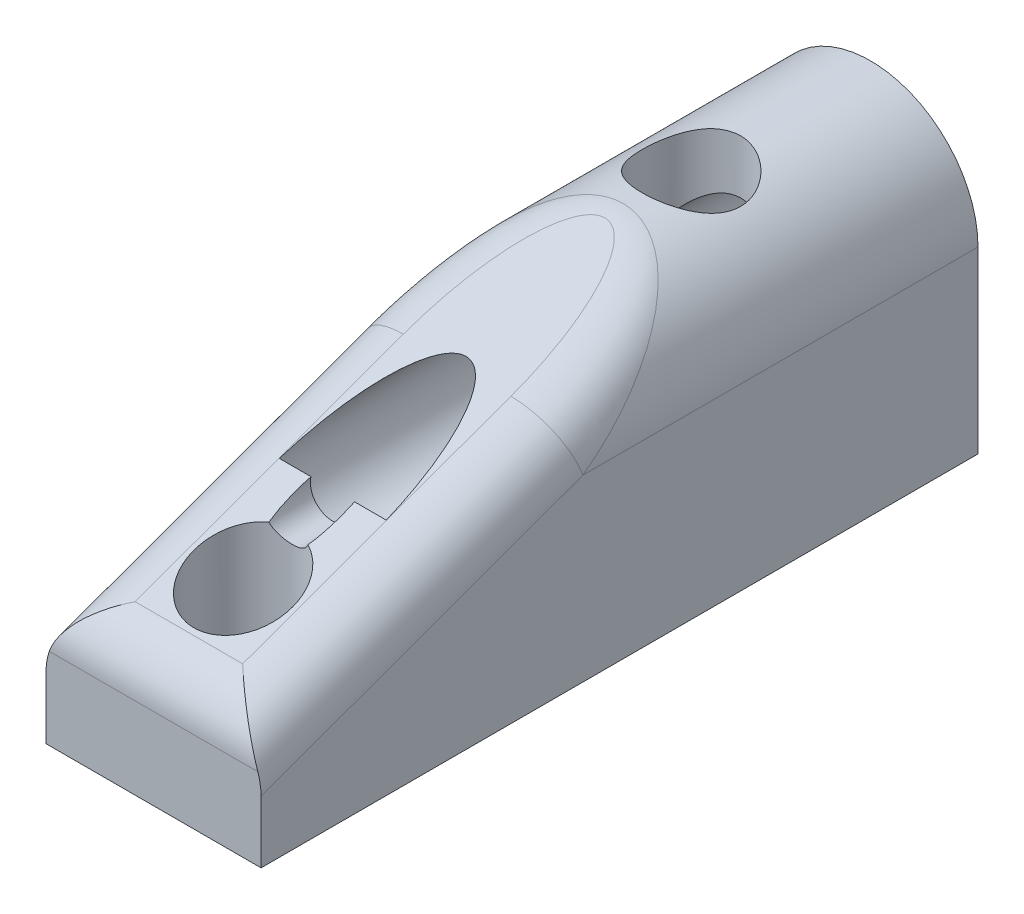
SolidWorks part; units mm, degrees
ref_plane "Ebene vorne" through (0, 0, 0) normal (0, 0, 1) x (1, 0, 0)
ref_plane "Ebene oben" through (0, 0, 0) normal (0, 1, 0) x (1, 0, 0)
ref_plane "Ebene rechts" through (0, 0, 0) normal (1, 0, 0) x (0, 0, -1)
sketch "Skizze1" plane through (0, 0, 0) normal (0, 0, 1) x (1, 0, 0)
  line L1 (-63.0762, -14.2199) -> (-23.0762, -14.2199)
  line L2 (-63.0762, -14.2199) -> (-63.0762, -26.2199)
  line L3 (-63.0762, -26.2199) -> (-23.0762, -26.2199)
  line L4 (-23.0762, -14.2199) -> (-23.0762, -26.2199)
  dimension "D1" = 12
  dimension "D2" = 40
extrude "Aufsatz-Linear austragen1" add sketch "Skizze1" along normal blind 63
sketch "Skizze2" plane through (0, 0, 0) normal (0, 0, -1) x (-1, 0, 0)
  line L0 (32.9762, -26.2199) -> (32.9762, -24.2199)
  line L1 (63.0762, -26.2199) -> (23.0762, -26.2199) construction
  line L2 (32.9762, -24.2199) -> (30.0063, -21.25)
  line L3 (30.0063, -21.25) -> (32.9762, -18.2802)
  line L4 (32.9762, -18.2802) -> (53.1762, -18.2802)
  line L5 (53.1762, -18.2802) -> (56.146, -21.25)
  line L6 (56.146, -21.25) -> (53.1762, -24.2199)
  line L7 (53.1762, -24.2199) -> (53.1762, -26.2199)
  line L9 (23.0762, -26.2199) -> (23.0762, -14.2199) construction
  dimension "D1" = 4.2
  dimension "D2" = 20.2
  dimension "D3" = 135
  dimension "D4" = 9.9
  dimension "D5" = 2
extrude "Schnitt-Linear austragen2" cut sketch "Skizze2" against normal through all and the other way through all flip side to cut
ref_plane "Ebene1" through (-43.0762, 0, 0) normal (1, 0, 0) x (0, 0, -1)
ref_axis "Achse1" through (-43.0762, -14.2199, 63) along (0, 1, 0)
hole_wizard "Stirnsenkung für M3" positions "Skizze12" profile "Skizze11" counterbore size "M4" standard "ISO" end condition through all
sketch "Skizze12" plane through (-23.0762, 0, 0) normal (1, 0, 0) x (0, 0, -1)
  line L0 (-63, -26.2199) -> (-63, -14.2199) construction
  line L1 (-63, -26.2199) -> (0, -26.2199) construction
  point P2 (-51, -21.2199)
  dimension "D1" = 12
  dimension "D2" = 5
sketch "Skizze11" plane through (-23.0762, -21.2199, 51) normal (0, 1, 0) x (0, 0, -1)
  line L0 (0, 0) -> (0, 40)
  line L1 (0, 40) -> (2.25, 40)
  line L3 (2.25, 40) -> (2.25, 4.4)
  line L4 (2.25, 4.4) -> (4, 4.4)
  line L5 (4, 4.4) -> (4, 0)
  line L7 (4, 0) -> (0, 0)
  line L11 (0, -6.35) -> (0, 107.95) construction
  dimension "Bohrerdurchmesser" = 4.5
  dimension "Bohrungstiefe" = 40
  dimension "Senkdurchmesser2" = 8
  dimension "Senktiefe2" = 4.4
sketch "Skizze13" plane through (-63.0762, 0, 0) normal (-1, 0, 0) x (0, 0, 1)
  line L1 (46.9585, -21.2199) -> (48.9793, -24.7199)
  line L2 (48.9793, -24.7199) -> (53.0207, -24.7199)
  line L3 (53.0207, -24.7199) -> (55.0415, -21.2199)
  line L4 (55.0415, -21.2199) -> (53.0207, -17.7199)
  line L5 (53.0207, -17.7199) -> (48.9793, -17.7199)
  line L6 (48.9793, -17.7199) -> (46.9585, -21.2199)
  circle A0 centre (51, -21.2199) radius 3.5 construction
  dimension "D1" = 7
extrude "Schnitt-Linear austragen3" cut sketch "Skizze13" against normal blind 3.2
pattern_linear "Lineares Muster2" count 2 spacing 39 along (0, 0, -1) of "Schnitt-Linear austragen3", "Stirnsenkung für M3"
sketch "Skizze14" plane through (-23.0762, 0, 0) normal (1, 0, 0) x (0, 0, -1)
  line L0 (0, -14.2199) -> (0, 15.7801)
  line L2 (0, 15.7801) -> (-3.3, 15.7801)
  line L3 (-60.5, -14.2199) -> (-13.2088, -7.0392)
  line L5 (-60.5, -14.2199) -> (0, -14.2199)
  line L6 (-63, -14.2199) -> (0, -14.2199) construction
  line L7 (-13.2088, -7.0392) -> (-3.3, 15.7801)
  dimension "D2" = 30
  dimension "D3" = 3.3
sketch "Skizze15" plane through (0, -14.2199, 0) normal (0, 1, 0) x (1, 0, 0)
  line L0 (-25.5762, 0) -> (-25.5762, -4)
  line L2 (-25.5762, -4) -> (-43.0762, -4)
  line L3 (-43.0762, -4) -> (-43.0762, 0)
  line L4 (-63.0762, 0) -> (-23.0762, 0) construction
  line L5 (-43.0762, 0) -> (-25.5762, 0)
  dimension "D1" = 4
  dimension "D2" = 2.5
chamfer "Fase1" distance 0.5 angle 45 23 edges at (-58.1262, -26.2199, 63) (-63.0762, -26.2199, 31.5) (-63.0762, -20.2199, 63) (-43.0762, -14.2199, 63) (-28.0262, -26.2199, 63) (-23.0762, -26.2199, 31.5) (-23.0762, -20.2199, 63) (-43.0762, -18.2802, 63) (-43.0762, -18.2802, 0) (-32.9762, -25.2199, 63) (-53.1762, -25.2199, 63) (-32.9762, -25.2199, 0) (-53.1762, -25.2199, 0) (-58.1262, -26.2199, 0) (-28.0262, -26.2199, 0) (-31.4913, -19.7651, 63) (-31.4913, -22.7349, 63) (-54.6611, -19.7651, 63) (-54.6611, -22.7349, 63) (-54.6611, -19.7651, 0) (-54.6611, -22.7349, 0) (-31.4913, -19.7651, 0) (-31.4913, -22.7349, 0)
sketch "Sketch1" plane through (0, -14.2199, 0) normal (0, 1, 0) x (1, 0, 0)
  line L0 (-43.0762, -21.7553) -> (-43.0762, 21.7553) construction
  line L1 (-37.0762, -48) -> (-49.0762, -48)
  line L2 (-37.0762, -48) -> (-37.0762, -8)
  line L3 (-37.0762, -8) -> (-49.0762, -8)
  line L4 (-49.0762, -48) -> (-49.0762, -8)
  line L5 (-37.0762, -48) -> (-49.0762, -8) construction
  line L6 (-37.0762, -8) -> (-49.0762, -48) construction
  point P0 (-43.0762, -28)
  dimension "D1" = 0
  dimension "D2" = 12
  dimension "D3" = 40
  dimension "D4" = 15
extrude "Boss-Extrude1" add sketch "Sketch1" along normal blind 10
sketch "Sketch2" plane through (0, 0, 48) normal (0, 0, 1) x (1, 0, 0)
  line L0 (-49.0762, -4.2199) -> (-37.0762, -4.2199) construction
  circle A0 centre (-43.0762, -4.2199) radius 6
extrude "Boss-Extrude2" add sketch "Sketch2" against normal blind 40
sketch "Sketch5" plane through (0, 0, 48) normal (0, 0, 1) x (1, 0, 0)
  line L0 (-37.0762, -4.2199) -> (-37.0762, -14.2199) construction
  circle A0 centre (-43.0762, -4.2199) radius 3
  dimension "D3" = 6
  dimension "D1" = 0
  dimension "D2" = 6
extrude "Cut-Extrude1" cut sketch "Sketch5" against normal blind 40 from offset 10 offset against normal yes
sketch "Sketch6" plane through (0, 0, 48) normal (0, 0, 1) x (1, 0, 0)
  line L0 (-37.0762, -4.2199) -> (-37.0762, -14.2199) construction
  circle A0 centre (-43.0762, -4.2199) radius 1.25
  dimension "D2" = 2.5
  dimension "D1" = 6
extrude "Cut-Extrude2" cut sketch "Sketch6" against normal through all
sketch "Sketch8" plane through (-43.0762, 0, 0) normal (1, 0, 0) x (0, 0, -1)
  line L0 (-51.094, -8.6906) -> (-9.7971, 6.3403)
  line L1 (-9.7971, 6.3403) -> (-51.094, 6.3403)
  line L2 (-51.094, 6.3403) -> (-51.094, -8.6906)
  dimension "D1" = 70
extrude "Cut-Extrude3" cut sketch "Sketch8" against normal through all and the other way through all
fillet "Fillet1" radius 3 4 edges at (-49.0762, -5.8922, 43.4054) (-43.0762, -7.5645, 48) (-37.0762, -5.8922, 43.4054) (-43.0762, 1.7801, 22.326)
sketch "Sketch9" plane through (0, -14.2199, 0) normal (0, 1, 0) x (1, 0, 0)
  line L0 (-49.0762, -48) -> (-37.0762, -48) construction
  line L1 (-37.0762, -48) -> (-37.0762, -8) construction
  line L2 (-37.0762, -8) -> (-49.0762, -8) construction
  circle A0 centre (-43.0762, -43) radius 1.5
  circle A1 centre (-43.0762, -18) radius 1.5
  dimension "D1" = 3
  dimension "D2" = 5
  dimension "D3" = 6
  dimension "D5" = 10
  dimension "D4" = 2
extrude "Cut-Extrude4" cut sketch "Sketch9" against normal through all and the other way through all
sketch "Sketch12" plane through (0, -14.2199, 14.2199) normal (0, -1, 0) x (1, 0, 0)
  line L3 (-49.0762, 33.7801) -> (-37.0762, 33.7801) construction
  circle A0 centre (-43.0762, 3.7801) radius 2.75
  circle A1 centre (-43.0762, 28.7801) radius 2.75
  point P2 (-43.0762, 33.7801)
  dimension "D1" = 5.5
  dimension "D2" = 5
  dimension "D4" = 2
extrude "Cut-Extrude5" cut sketch "Sketch12" against normal blind 30 from offset 2.5 offset against normal yes
sketch "Sketch14" plane through (-63.0762, 0, 0) normal (-1, 0, 0) x (0, 0, 1)
  line L0 (63, -14.7199) -> (63, -25.7199) construction
  line L1 (0, -14.2199) -> (63, -14.2199)
  line L2 (0, -14.2199) -> (0, -32.6212)
  line L3 (0, -32.6212) -> (63, -32.6212)
  line L4 (63, -14.2199) -> (63, -32.6212)
  line L5 (24.2947, -32.0862) -> (22.2986, -32.0862)
  line L6 (24.2947, -32.0862) -> (24.2947, -26.5291)
  line L7 (24.2947, -26.5291) -> (22.2986, -26.5291)
  line L8 (22.2986, -32.0862) -> (22.2986, -26.5291)
  dimension "D1" = 0
extrude "Cut-Extrude6" cut sketch "Sketch14" against normal through all
